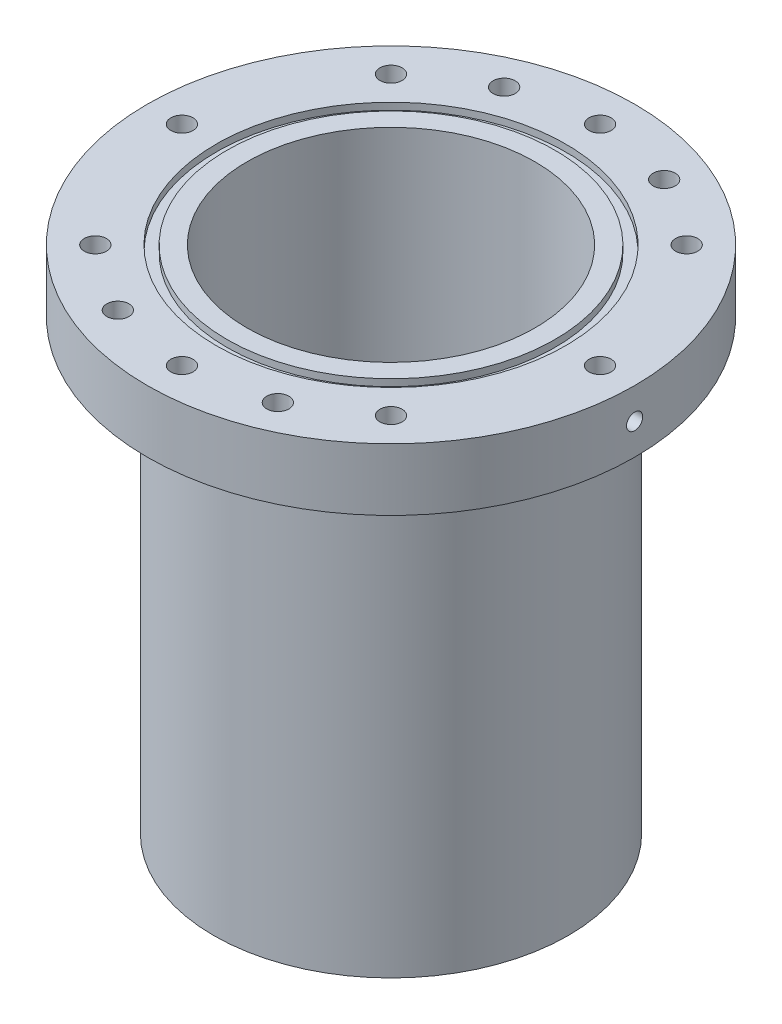
SolidWorks part; units mm, degrees
ref_plane "Front Plane" through (0, 0, 0) normal (0, 0, 1) x (1, 0, 0)
ref_plane "Top Plane" through (0, 0, 0) normal (0, 1, 0) x (1, 0, 0)
ref_plane "Right Plane" through (0, 0, 0) normal (1, 0, 0) x (0, 0, -1)
sketch "Sketch2" plane through (0, 0, 0) normal (0, 1, 0) x (1, 0, 0)
  circle A0 centre (0, 0) radius 41.275
  circle A1 centre (0, 0) radius 50.8
  dimension "D1" = 101.6
  dimension "D2" = 82.55
extrude "Base Cylinder" add sketch "Sketch2" along normal blind 292.1
sketch "Sketch3" plane through (0, 0, 0) normal (0, -1, 0) x (1, 0, 0)
  circle A0 centre (0, 0) radius 41.275
  circle A1 centre (0, 0) radius 69.85
  dimension "D1" = 139.7
extrude "Aft Flange" add sketch "Sketch3" against normal blind 17.78
sketch "Sketch4" plane through (0, 292.1, 0) normal (0, 1, 0) x (1, 0, 0)
  circle A0 centre (0, 0) radius 41.275
  circle A1 centre (0, 0) radius 69.85
extrude "Forward Flange" add sketch "Sketch4" against normal blind 17.78
sketch "Sketch6" plane through (0, 0, 0) normal (0, -1, 0) x (1, 0, 0)
  circle A0 centre (0, 0) radius 50.0761
  circle A1 centre (0, 0) radius 47.0027
  dimension "D1" = 100.1522
  dimension "D2" = 94.0054
extrude "O-Ring Slot 1" cut sketch "Sketch6" against normal blind 1.9812
sketch "Sketch7" plane through (0, 292.1, 0) normal (0, 1, 0) x (1, 0, 0)
  circle A0 centre (0, 0) radius 50.0761
  circle A1 centre (0, 0) radius 47.0027
  dimension "D1" = 100.1522
  dimension "D2" = 94.0054
extrude "O-Ring Slot 2" cut sketch "Sketch7" against normal blind 1.9812
sketch "Sketch8" plane through (0, 0, 0) normal (0, -1, 0) x (1, 0, 0)
  circle A0 centre (-59.9186, 0) radius 3.175
  circle A1 centre (-42.3688, 42.3688) radius 3.175
  circle A2 centre (0, 59.9186) radius 3.175
  circle A3 centre (42.3688, 42.3688) radius 3.175
  circle A4 centre (59.9186, 0) radius 3.175
  circle A5 centre (42.3688, -42.3688) radius 3.175
  circle A6 centre (0, -59.9186) radius 3.175
  circle A7 centre (-42.3688, -42.3688) radius 3.175
  point P36 (0, 0)
  dimension "D2" = 6.35
  dimension "D1" = 59.9186
  dimension "D3" = 8
extrude "Cut-Extrude4" cut sketch "Sketch8" against normal through all both and the other way through all
fillet "Fillet1" radius 4.7625 2 edges at (0, 17.78, -50.8) (0, 274.32, 50.8)
sketch "Sketch9" plane through (0, 292.1, 0) normal (0, 1, 0) x (1, 0, 0)
  line L0 (0, -76.2) -> (0, 76.2) construction
  line L1 (-32.6024, 78.7092) -> (32.6024, -78.7092) construction
  line L2 (-32.0538, -77.3847) -> (32.0538, 77.3847) construction
  circle A0 centre (0, 0) radius 59.9186 construction
  circle A1 centre (-22.9299, 55.3576) radius 3.175
  circle A2 centre (22.9299, -55.3576) radius 3.175
  circle A3 centre (22.9299, 55.3576) radius 3.175
  circle A4 centre (-22.9299, -55.3576) radius 3.175
  point P6 (0, 0)
  point P9 (0, 0)
  point P16 (0, 0)
  dimension "D1" = 119.8372
  dimension "D3" = 6.35
  dimension "D4" = 6.35
  dimension "D5" = 6.35
  dimension "D6" = 6.35
  dimension "D2" = 22.5
  dimension "D7" = 22.5
extrude "Cut-Extrude5" cut sketch "Sketch9" against normal blind 7.62
sketch "Sketch10" plane through (0, 0, 0) normal (0, -1, 0) x (1, 0, 0)
  line L0 (0, -76.2) -> (0, 76.2) construction
  line L1 (-33.7592, 81.5019) -> (33.7592, -81.5019) construction
  line L2 (-33.8465, -81.7128) -> (33.8465, 81.7128) construction
  circle A0 centre (0, 0) radius 59.9186 construction
  circle A1 centre (-22.9299, 55.3576) radius 3.175
  circle A2 centre (22.9299, -55.3576) radius 3.175
  circle A3 centre (22.9299, 55.3576) radius 3.175
  circle A4 centre (-22.9299, -55.3576) radius 3.175
  point P6 (0, 0)
  point P9 (0, 0)
  point P16 (0, 0)
  dimension "D1" = 119.8372
  dimension "D2" = 6.35
  dimension "D3" = 6.35
  dimension "D5" = 6.35
  dimension "D6" = 6.35
  dimension "D4" = 22.5
  dimension "D7" = 22.5
extrude "Cut-Extrude6" cut sketch "Sketch10" against normal blind 7.62
sketch "Sketch11" plane through (0, 284.48, 0) normal (0, 1, 0) x (1, 0, 0)
  circle A0 centre (-22.9299, 55.3576) radius 1.4097
  circle A1 centre (22.9299, 55.3576) radius 1.4097
  circle A2 centre (-22.9299, -55.3576) radius 1.4097
  circle A3 centre (22.9299, -55.3576) radius 1.4097
  dimension "D1" = 2.8194
  dimension "D2" = 2.8194
  dimension "D3" = 2.8194
  dimension "D4" = 2.8194
extrude "Cut-Extrude7" cut sketch "Sketch11" against normal up to next
sketch "Sketch12" plane through (0, 7.62, 0) normal (0, -1, 0) x (1, 0, 0)
  circle A0 centre (-22.9299, 55.3576) radius 1.4097
  circle A1 centre (22.9299, 55.3576) radius 1.4097
  circle A2 centre (-22.9299, -55.3576) radius 1.4097
  circle A3 centre (22.9299, -55.3576) radius 1.4097
  dimension "D1" = 2.8194
  dimension "D2" = 2.8194
  dimension "D3" = 2.8194
  dimension "D4" = 2.8194
extrude "Cut-Extrude8" cut sketch "Sketch12" against normal up to next
ref_plane "Plane1" through (-69.85, 0, 0) normal (1, 0, 0) x (0, 0, -1)
ref_plane "Plane3" through (69.85, 0, 0) normal (1, 0, 0) x (0, 0, -1)
ref_plane "Plane4" through (0, 283.21, 0) normal (0, 1, 0) x (1, 0, 0)
sketch "Sketch13" plane through (-69.85, 0, 0) normal (1, 0, 0) x (0, 0, -1)
  line L0 (76.835, 283.21) -> (-76.835, 283.21) construction
  circle A0 centre (0, 283.21) radius 2.3114
  dimension "D1" = 4.6228
extrude "Cut-Extrude10" cut sketch "Sketch13" along normal blind 6.35
sketch "Sketch14" plane through (69.85, 0, 0) normal (1, 0, 0) x (0, 0, -1)
  circle A0 centre (0, 283.21) radius 2.3114
  dimension "D1" = 4.6228
extrude "Cut-Extrude11" cut sketch "Sketch14" against normal blind 6.35
ref_axis "Axis1" through (63.5, 283.21, 0) along (1, 0, 0)
ref_axis "Axis2" through (-63.5, 283.21, 0) along (-1, 0, 0)
sketch "Sketch17" plane through (0, 0, 0) normal (0, -1, 0) x (-1, 0, 0)
  circle A0 centre (0, 0) radius 69.85
extrude "Cut-Extrude12" cut sketch "Sketch17" against normal blind 146.05
